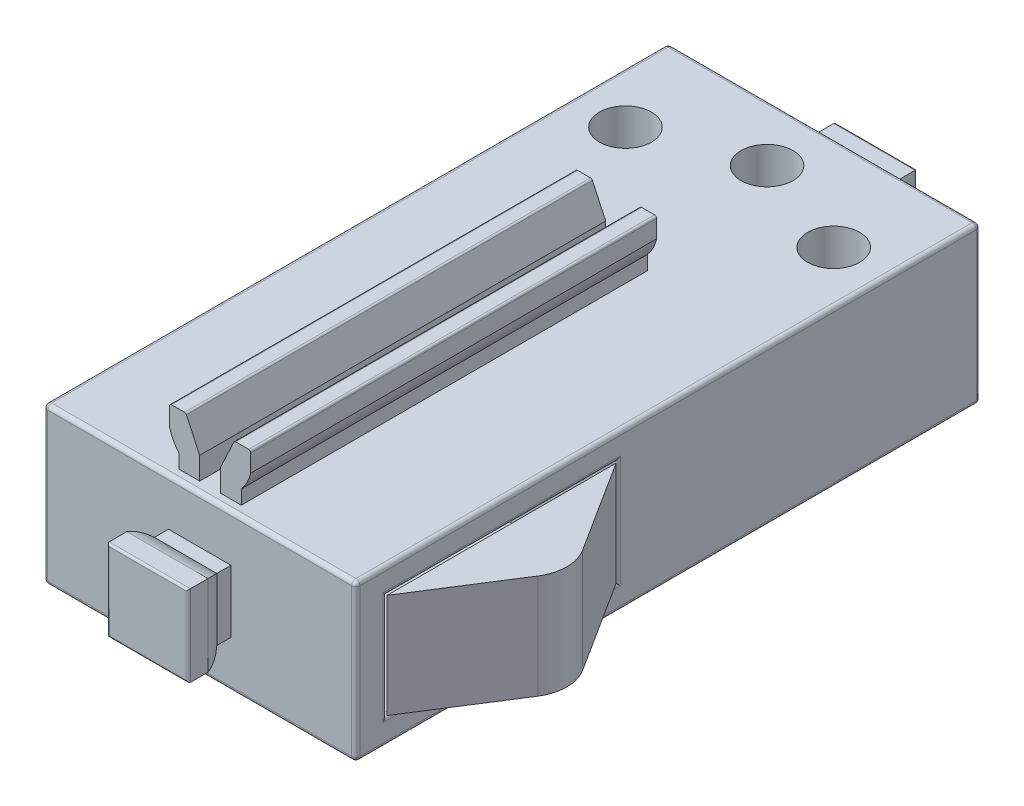
SolidWorks part; units mm, degrees
ref_plane "前视基准面" through (0, 0, 0) normal (0, 0, 1) x (1, 0, 0)
ref_plane "上视基准面" through (0, 0, 0) normal (0, 1, 0) x (1, 0, 0)
ref_plane "右视基准面" through (0, 0, 0) normal (1, 0, 0) x (0, 0, -1)
sketch "草图2" plane through (0, 0, 0) normal (0, 0, 1) x (1, 0, 0)
  line L1 (-7.5, 0) -> (7.5, 0)
  line L2 (-7.5, 0) -> (-7.5, -7.5)
  line L3 (-7.5, -7.5) -> (7.5, -7.5)
  line L4 (7.5, 0) -> (7.5, -7.5)
extrude "凸台-拉伸1" add sketch "草图2" against normal blind 30
sketch "草图3" plane through (0, 0, 0) normal (0, 0, 1) x (1, 0, 0)
  line L0 (-8, -3.75) -> (8, -3.75) construction
  line L1 (-1.5, -5.25) -> (1.5, -5.25)
  line L2 (-1.5, -5.25) -> (-1.5, -2.25)
  line L3 (-1.5, -2.25) -> (1.5, -2.25)
  line L4 (1.5, -5.25) -> (1.5, -2.25)
extrude "凸台-拉伸2" add sketch "草图3" along normal blind 1
sketch "草图4" plane through (0, -5.25, 0) normal (0, -1, 0) x (1, 0, 0)
  line L0 (-1.95, 2.5) -> (1.95, 2.5)
  line L1 (-1.95, 2.5) -> (-1.95, 1.5556)
  line L2 (1.95, 2.5) -> (1.95, 1.5556)
  line L4 (-1.5, 1) -> (-1.5, 0) construction
  line L5 (-1.5, 0.6771) -> (1.5, 0.6771)
  arc A0 (1.5, 0.6771) -> (1.95, 1.5556) centre (0, 2) ccw
  arc A2 (-1.95, 1.5556) -> (-1.5, 0.6771) centre (0, 2) ccw
extrude "凸台-拉伸3" add sketch "草图4" along normal blind 1 and the other way blind 4
sketch "草图5" plane through (-1.95, 0, 0) normal (-1, 0, 0) x (0, 0, 1)
  line L0 (2.5, -5.7) -> (2.5, -6.25)
  line L1 (2.5, -1.8) -> (1.5556, -1.8)
  line L2 (2.5, -1.25) -> (2.5, -1.8)
  line L3 (0.6771, -2.25) -> (0.6771, -1.25)
  line L4 (0.6771, -1.25) -> (2.5, -1.25)
  line L5 (0.6771, -5.25) -> (0.6771, -6.25)
  line L6 (0.6771, -6.25) -> (2.5, -6.25)
  line L7 (2.5, -5.7) -> (1.5556, -5.7)
  arc A0 (0.6771, -5.25) -> (1.5556, -5.7) centre (2, -3.75) ccw
  arc A1 (1.5556, -1.8) -> (0.6771, -2.25) centre (2, -3.75) ccw
extrude "切除-拉伸1" cut sketch "草图5" against normal up to next
fillet "圆角1" radius 0.1 4 edges at (1.95, -3.75, 2.5) (0, -5.7, 2.5) (-1.95, -3.75, 2.5) (0, -1.8, 2.5)
ref_plane "基准面1" through (0, 0, -15) normal (0, 0, 1) x (1, 0, 0)
mirror "镜向3" about plane through (0, 0, -15) normal (0, 0, 1) of "凸台-拉伸2", "凸台-拉伸3", "切除-拉伸1", "圆角1"
sketch "草图7" plane through (0, 0, 0) normal (0, 0, 1) x (1, 0, 0)
  line L0 (-1.5, 0) -> (-1.5, 0.6771)
  line L1 (7.5, 0) -> (-7.5, 0) construction
  line L2 (-1.95, 2.5) -> (-1.1658, 2.5)
  line L3 (1.5, 0.6771) -> (1.5, 0)
  line L4 (1.5, 0) -> (0.5, 0)
  line L5 (-1.95, 2.5) -> (-1.95, 1.5556)
  line L6 (1.95, 2.5) -> (1.95, 1.5556)
  line L7 (-0.5, 1.0723) -> (-0.5, 0)
  line L8 (0.5, 1.0723) -> (0.5, 0)
  line L9 (1.1658, 2.5) -> (1.95, 2.5)
  line L10 (-0.5, 0) -> (-1.5, 0)
  line L11 (-0.5, 1.0723) -> (-1.1658, 2.5)
  line L12 (0.5, 1.0723) -> (1.1658, 2.5)
  arc A0 (1.5, 0.6771) -> (1.95, 1.5556) centre (0, 2) ccw
  arc A1 (-1.95, 1.5556) -> (-1.5, 0.6771) centre (0, 2) ccw
extrude "凸台-拉伸4" add sketch "草图7" against normal blind 19.5 from offset 0.5 offset against normal yes
sketch "草图8" plane through (-7.5, 0, 0) normal (-1, 0, 0) x (0, 0, 1)
  line L1 (-12.5, -6.25) -> (-1.5, -6.25)
  line L2 (-12.5, -6.25) -> (-12.5, -1.25)
  line L3 (-12.5, -1.25) -> (-1.5, -1.25)
  line L4 (-1.5, -6.25) -> (-1.5, -1.25)
extrude "切除-拉伸2" cut sketch "草图8" against normal up to next
sketch "草图9" plane through (0, -7.5, 0) normal (0, -1, 0) x (1, 0, 0)
  line L0 (7.5, -1.5) -> (7.5, -12.5)
  line L1 (7.5, -30) -> (7.5, 0) construction
  line L3 (11, -7) -> (7.5, -1.5)
  line L4 (11, -7) -> (7.5, -12.5)
extrude "凸台-拉伸5" add sketch "草图9" against normal blind 5 from offset 1.25 separate body offset against normal yes
fillet "圆角4" radius 2 1 edges at (11, -3.75, -7)
sketch "草图10" plane through (0, -6.25, 0) normal (0, -1, 0) x (1, 0, 0)
  line L0 (8, -4) -> (8, -10)
  line L2 (10, -7) -> (8, -4)
  line L3 (10, -7) -> (8, -10)
extrude "切除-拉伸3" cut sketch "草图10" against normal blind 4
fillet "圆角5" radius 2 1 edges at (10, -4.25, -7)
sketch "草图11" plane through (0, 0, 0) normal (0, 1, 0) x (-1, 0, 0)
  circle A0 centre (0, -27.25) radius 1.25
  circle A1 centre (5, -25.45) radius 1.25
  circle A2 centre (-5, -25.45) radius 1.25
extrude "切除-拉伸4" cut sketch "草图11" against normal up to next (7.5 mm away)
fillet "圆角2" radius 0.1 4 edges at (1.1658, 2.5, -10.25) (1.95, 2.5, -10.25) (-1.95, 2.5, -10.25) (-1.1658, 2.5, -10.25)
fillet "圆角3" radius 0.2 20 edges at (-7.5, -7.5, -15) (-7.5, -3.75, -30) (-7.5, 0, -15) (-7.5, -3.75, 0) (7.5, 0, -15) (7.5, -3.75, -30) (7.5, -7.5, -15) (7.5, -3.75, 0) (0, -7.5, -30) (0, 0, -30) (0, -7.5, 0) (0, 0, 0) (-7.5, -6.25, -7) (-7.5, -3.75, -1.5) (-7.5, -1.25, -7) (-7.5, -3.75, -12.5) (7.5, -1.25, -7) (7.5, -3.75, -1.5) (7.5, -6.25, -7) (7.5, -3.75, -12.5)
sketch "草图12" plane through (0, -7.5, 0) normal (0, -1, 0) x (1, 0, 0)
  line L0 (0, -12) -> (0, -22) construction
  line L1 (-0.2, -12.4583) -> (-0.2, -22)
  line L2 (0.2, -12.4583) -> (0.2, -22)
  line L3 (-0.2, -22) -> (0.2, -22)
  line L4 (-1.5, -9) -> (-2.2261, -9)
  line L5 (-0.2, -12) -> (-0.2, -22) construction
  line L6 (0.2, -12) -> (0.2, -22) construction
  line L7 (-5.5, -9) -> (-5.5, -21)
  line L8 (-1.5, -9.4) -> (-1.8699, -9.4)
  line L9 (-5.1, -9.4) -> (-5.1, -21)
  line L10 (-1.5, -9) -> (-1.5, -9.4)
  line L11 (-5.5, -21) -> (-5.1, -21)
  line L12 (5.5, -21) -> (5.1, -21)
  line L13 (1.5, -9) -> (1.5, -9.4)
  line L14 (1.5, -9.4) -> (5.1, -9.4)
  line L15 (1.5, -9) -> (5.5, -9)
  line L16 (5.1, -9.4) -> (5.1, -21)
  line L17 (5.5, -9) -> (5.5, -21)
  line L18 (0, -11.5) -> (-1.8699, -9.4)
  line L19 (-3.325, -7.7658) -> (-3.6237, -8.0318)
  line L20 (-3.6237, -8.0318) -> (-2.7616, -9)
  line L21 (-2.7616, -9) -> (-5.5, -9)
  line L22 (-2.4055, -9.4) -> (-5.1, -9.4)
  line L23 (-1.5, -9) -> (-5.5, -9) construction
  line L24 (-2.4055, -9.4) -> (-0.3799, -11.6749)
  line L25 (-1.5, -9.4) -> (-5.1, -9.4) construction
  line L26 (-2.2261, -9) -> (-3.325, -7.7658)
  arc A0 (0.2, -12.4583) -> (0, -11.5) centre (0, -12) ccw
  arc A1 (-0.3799, -11.6749) -> (-0.2, -12.4583) centre (0, -12) ccw
  dimension "D5" = 1
  dimension "D1" = 12
  dimension "D2" = 10
  dimension "D6" = 9
  dimension "D7" = 1.5
  dimension "D8" = 4
  dimension "D9" = 12
  dimension "D11" = 5
  dimension "D12" = 0.4
  dimension "D3" = 0.2
  dimension "D4" = 0.2
  dimension "D10" = 0.4
wrap "包覆1" sketch "草图12" wrap type scribe source sketch "草图12" face at (0, -7.5, -15)
